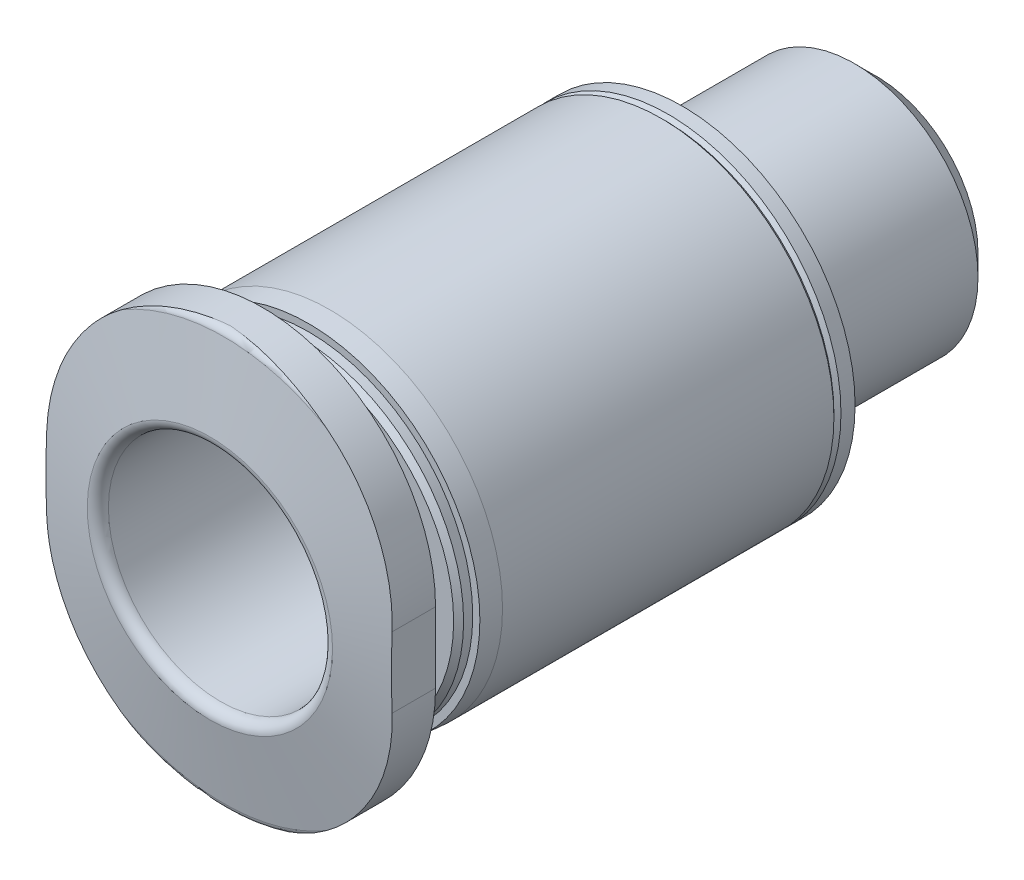
SolidWorks part; units mm, degrees
ref_plane "Ebene vorne" through (0, 0, 0) normal (0, 0, 1) x (1, 0, 0)
ref_plane "Ebene oben" through (0, 0, 0) normal (0, 1, 0) x (1, 0, 0)
ref_plane "Ebene rechts" through (0, 0, 0) normal (1, 0, 0) x (0, 0, -1)
sketch "Skizze1" plane through (0, 0, 0) normal (1, 0, 0) x (0, 0, -1)
  line L0 (-13.4, 0) -> (-13.4, 3.4785)
  line L1 (-13.4, 3.4785) -> (-13.0022, 5.7347)
  line L2 (-12.8052, 5.9) -> (-11.9, 5.9)
  line L3 (-11.9, 5.9) -> (-11.9, 4.2535)
  line L4 (-11.525, 3.8785) -> (-11, 3.8785)
  line L5 (-11, 3.8785) -> (-11, 4.5136)
  line L6 (-11, 4.5136) -> (-10.8586, 4.655)
  line L7 (-10.8586, 4.655) -> (-10.6, 4.655)
  line L8 (-10.6, 4.655) -> (-10.6, 4.858)
  line L9 (-10.6, 4.858) -> (-10, 4.9)
  line L10 (-10, 4.9) -> (-0.6, 4.9)
  line L11 (-0.6, 4.9) -> (-0.5, 4.8)
  line L12 (-0.5, 4.8) -> (-0.4, 4.9)
  line L13 (-0.4, 4.9) -> (0, 4.9)
  line L14 (0, 4.9) -> (0, 3.5)
  line L15 (0, 3.5) -> (4.8865, 3.5)
  line L16 (4.8865, 3.5) -> (5.5, 2.8865)
  line L17 (5.5, 2.8865) -> (5.5, 0)
  line L18 (5.5, 0) -> (-13.4, 0)
  line L19 (5.5, 0) -> (-13.4, 0) construction
  arc A0 (-13.0022, 5.7347) -> (-12.8052, 5.9) centre (-12.8052, 5.7) cw
  arc A1 (-11.9, 4.2535) -> (-11.525, 3.8785) centre (-11.525, 4.2535) ccw
revolve "Rotation1" add sketch "Skizze1" angle 360 about L19 reverse direction yes
cosmetic thread "Gewindedarstellung1" parameters "D1"=5, "D2"=5.773
ref_plane "Ebene1" through (-13.4, 0, 0) normal (1, 0, 0) x (0, 0, -1)
ref_plane "Ebene2" through (0, 0, 13.4) normal (0, 0, 1) x (1, 0, 0)
sketch "Skizze2" plane through (0, 0, 13.4) normal (0, 0, 1) x (1, 0, 0)
  line L0 (-11.8, 11.8) -> (-11.8, -11.8)
  line L1 (-11.8, -11.8) -> (11.8, -11.8)
  line L2 (11.8, -11.8) -> (11.8, 11.8)
  line L3 (11.8, 11.8) -> (-11.8, 11.8)
  line L4 (4.9, -1) -> (4.9, 1)
  line L5 (-4.9, 1) -> (-4.9, -1)
  arc A0 (-4.9, -1) -> (4.9, -1) centre (0, -1) ccw
  arc A1 (4.9, 1) -> (-4.9, 1) centre (0, 1) ccw
extrude "Linear austragen1" cut sketch "Skizze2" against normal blind 1.5
ref_plane "Ebene3" through (0, 0, -5.5) normal (0, 0, 1) x (1, 0, 0)
sketch "Skizze3" plane through (0, 0, -5.5) normal (0, 0, 1) x (1, 0, 0)
  line L0 (-2, 1.1547) -> (-2, -1.1547)
  line L1 (-2, -1.1547) -> (0, -2.3094)
  line L2 (0, -2.3094) -> (2, -1.1547)
  line L3 (2, -1.1547) -> (2, 1.1547)
  line L4 (2, 1.1547) -> (0, 2.3094)
  line L5 (0, 2.3094) -> (-2, 1.1547)
extrude "Linear austragen2" cut sketch "Skizze3" along normal blind 7.2
sketch "Skizze4" plane through (0, 0, 0) normal (1, 0, 0) x (0, 0, -1)
  line L0 (-13.4, 0) -> (-13.4, 3.4785)
  line L1 (-13.1, 3.1785) -> (-1.7, 3.1785)
  line L2 (-1.7, 3.1785) -> (-1.7, 0)
  line L3 (-1.7, 0) -> (-13.4, 0)
  line L4 (-1.7, 0) -> (-13.4, 0) construction
  arc A0 (-13.4, 3.4785) -> (-13.1, 3.1785) centre (-13.1, 3.4785) ccw
revolve "Schnitt-Rotation1" cut sketch "Skizze4" angle 360 about L4 reverse direction yes
ref_plane "ANBAU XY" through (0, 0, 0) normal (0, 0, -1) x (-1, 0, 0)
ref_plane "ANBAU XZ" through (0, 0, 0) normal (0, 1, 0) x (-1, 0, 0)
ref_plane "ANBAU YZ" through (0, 0, 0) normal (1, 0, 0) x (0, 0, -1)
ref_axis "ANBAU X" through (-80.9, 0, 0) along (1, 0, 0)
ref_axis "ANBAU Y" through (0, 50, 0) along (0, -1, 0)
ref_axis "ANBAU Z" through (0, 0, -80.9) along (0, 0, 1)
sketch3d "ANBAU"
  point P0 (0, 0, 0)
ref_plane "CPV XY" through (0, 0, 0) normal (0, 0, 1) x (1, 0, 0)
ref_plane "CPV XZ" through (0, 0, 0) normal (0, -1, 0) x (1, 0, 0)
ref_plane "CPV YZ" through (0, 0, 0) normal (1, 0, 0) x (0, 0, -1)
ref_axis "CPV X" through (-80.9, 0, 0) along (1, 0, 0)
ref_axis "CPV Y" through (0, -50, 0) along (0, 1, 0)
ref_axis "CPV Z" through (0, 0, 80.9) along (0, 0, -1)
sketch3d "CPV"
  point P0 (0, 0, 0)
ref_plane "CPV_ANBAU XY" through (0, 0, 0) normal (0, 0, 1) x (1, 0, 0)
ref_plane "CPV_ANBAU XZ" through (0, 0, 0) normal (0, -1, 0) x (1, 0, 0)
ref_plane "CPV_ANBAU YZ" through (0, 0, 0) normal (1, 0, 0) x (0, 0, -1)
ref_axis "CPV_ANBAU X" through (-80.9, 0, 0) along (1, 0, 0)
ref_axis "CPV_ANBAU Y" through (0, -50, 0) along (0, 1, 0)
ref_axis "CPV_ANBAU Z" through (0, 0, 80.9) along (0, 0, -1)
sketch3d "CPV_ANBAU"
  point P0 (0, 0, 0)
